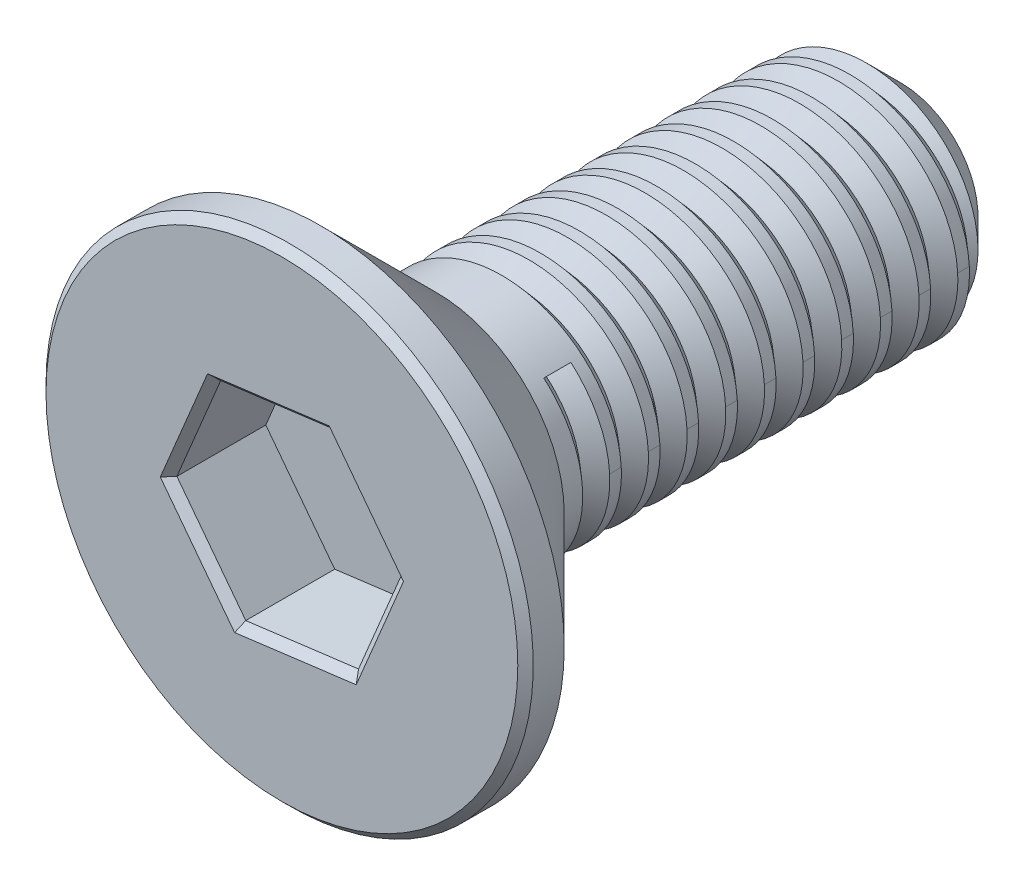
SolidWorks part; units mm, degrees
material "冷轧钢板"
ref_plane "前视基准面" through (0, 0, 0) normal (0, 0, 1) x (1, 0, 0)
ref_plane "上视基准面" through (0, 0, 0) normal (0, 1, 0) x (1, 0, 0)
ref_plane "右视基准面" through (0, 0, 0) normal (1, 0, 0) x (0, 0, -1)
sketch "草图1" plane through (0, 0, 0) normal (0, 0, 1) x (1, 0, 0)
  circle A0 centre (0, 0) radius 6.3
  dimension "D1" = 12.6
extrude "凸台-拉伸1" add sketch "草图1" along normal blind 1
sketch "草图2" plane through (0, 0, 0) normal (0, 1, 0) x (1, 0, 0)
  line L0 (0, 0) -> (0, 3)
  line L1 (0, 3) -> (-3.3, 3)
  line L2 (-3.3, 3) -> (-6.3, 0)
  line L3 (-6.3, 0) -> (0, 0)
  dimension "D1" = 3
  dimension "D2" = 3.3
revolve "旋转2" add sketch "草图2" angle 360 about L0
sketch "草图3" plane through (0, 0, -3) normal (0, 0, -1) x (-1, 0, 0)
  circle A0 centre (0, 0) radius 3
  dimension "D1" = 6
extrude "凸台-拉伸2" add sketch "草图3" along normal blind 12
sketch "草图4" plane through (0, 0, 1) normal (0, 0, 1) x (1, 0, 0)
  line L1 (1.1343, 2.712) -> (-1.7815, 2.3383)
  line L2 (-1.7815, 2.3383) -> (-2.9158, -0.3737)
  line L3 (-2.9158, -0.3737) -> (-1.1343, -2.712)
  line L4 (-1.1343, -2.712) -> (1.7815, -2.3383)
  line L5 (1.7815, -2.3383) -> (2.9158, 0.3737)
  line L6 (2.9158, 0.3737) -> (1.1343, 2.712)
  circle A0 centre (0, 0) radius 2.5458 construction
extrude "切除-拉伸1" cut sketch "草图4" against normal blind 2.5
chamfer "倒角1" distance 1 angle 45 1 edges at (-3, 0, -15)
sketch "草图5" plane through (0, 0, -15) normal (0, 0, -1) x (-1, 0, 0)
  circle A0 centre (0, 0) radius 3
curve "螺旋线/涡状线1" pitch 1 height 11 radius 3 centre (0, 0, -15) axis (0, 0, 1) start towards (0.7071, 0.7071, 0)
sketch "草图6" plane through (0, 0, 0) normal (1, 0, 0) x (0, 0, -1)
  line L0 (14.525, 3) -> (15.225, 3)
  line L1 (14.875, 3) -> (14.875, 2.6) construction
  line L2 (14.525, 3) -> (14.875, 2.6)
  line L3 (14.875, 2.6) -> (15.225, 3)
  dimension "D1" = 0.7
  dimension "D2" = 0.4
sweep "切除-扫描1" cut profiles "草图6" path "螺旋线/涡状线1" align with end faces yes
chamfer "倒角2" distance 0.2 angle 45 7 edges at (6.3, 0, 1) (-0.3236, 2.5251, 1) (-2.3486, 0.9823, 1) (-2.025, -1.5428, 1) (0.3236, -2.5251, 1) (2.3486, -0.9823, 1) (2.025, 1.5428, 1)
